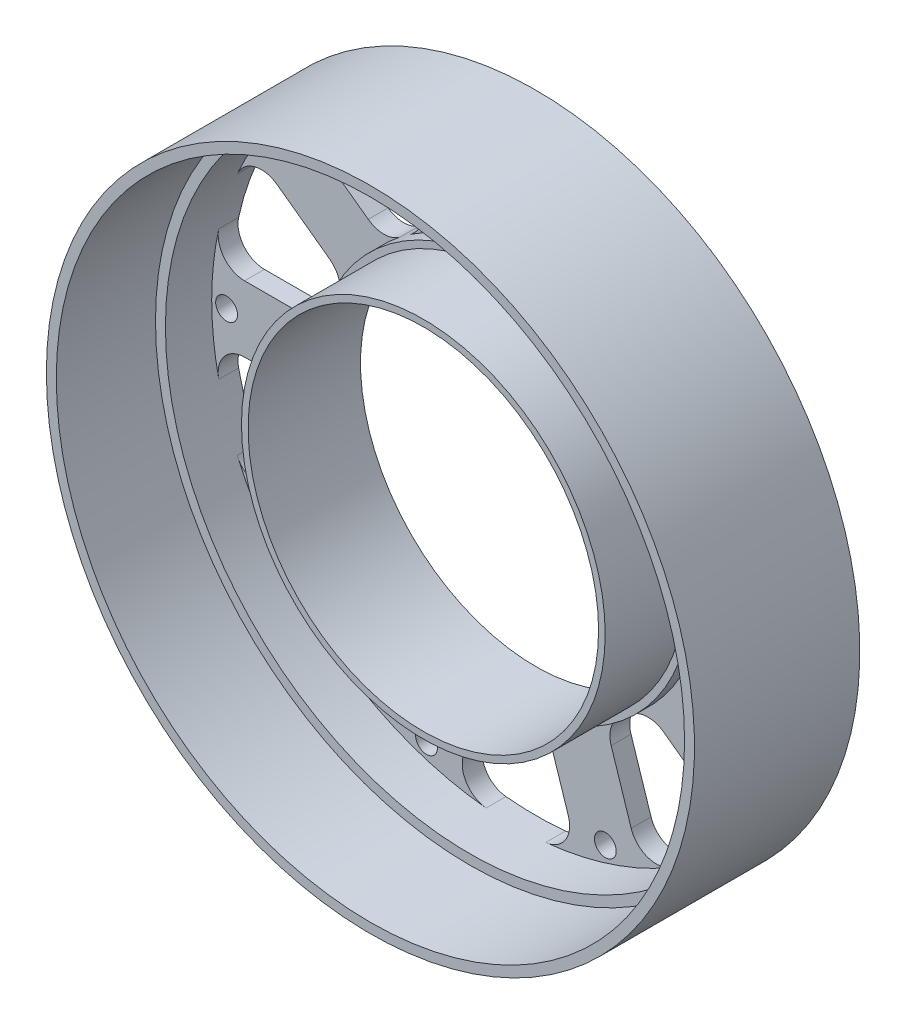
SolidWorks part; units mm, degrees
ref_plane "Front Plane" through (0, 0, 0) normal (0, 0, 1) x (1, 0, 0)
ref_plane "Top Plane" through (0, 0, 0) normal (0, 1, 0) x (1, 0, 0)
ref_plane "Right Plane" through (0, 0, 0) normal (1, 0, 0) x (0, 0, -1)
sketch "Sketch1" plane through (0, 0, 0) normal (0, 0, 1) x (1, 0, 0)
  circle A0 centre (0, 0) radius 27.5
  circle A1 centre (0, 0) radius 26.5
  circle A2 centre (0, 0) radius 28.5
  dimension "D1" = 55
  dimension "D2" = 53
  dimension "D3" = 57
extrude "Boss-Extrude2" add sketch "Sketch1" along normal blind 12 contours A0 A1 region at (-26.7222, 0, 0)
extrude "Boss-Extrude3" add sketch "Sketch1<3>" against normal blind 5 contours A2 A0 | A0 A1 region at (-26.7222, 0, 0) region at (-27.6939, 0, 0)
sketch "Sketch1<3>" plane through (0, 0, 0) normal (0, 0, 1) x (1, 0, 0) same geometry as "Sketch1"
sketch "Sketch3" plane through (0, 0, -5) normal (0, 0, -1) x (-1, 0, 0)
  line L0 (0, -1000) -> (0, 49000) construction
  line L1 (0, 0) -> (47.5, 0) construction
  line L2 (28.058, 5) -> (47.2361, 5)
  line L3 (28.058, -5) -> (47.2361, -5)
  line L4 (25.6383, -12.447) -> (41.1537, -23.7196)
  line L5 (19.7605, -20.5371) -> (35.2759, -31.8098)
  line L6 (13.4257, -25.1396) -> (19.352, -43.3791)
  line L7 (3.9151, -28.2298) -> (9.8415, -46.4693)
  line L8 (-3.9151, -28.2298) -> (-9.8415, -46.4693)
  line L9 (-13.4257, -25.1396) -> (-19.352, -43.3791)
  line L10 (-19.7605, -20.5371) -> (-35.2759, -31.8098)
  line L11 (-25.6383, -12.447) -> (-41.1537, -23.7196)
  line L12 (-28.058, -5) -> (-47.2361, -5)
  line L13 (-28.058, 5) -> (-47.2361, 5)
  line L14 (-25.6383, 12.447) -> (-41.1537, 23.7196)
  line L15 (-19.7605, 20.5371) -> (-35.2759, 31.8098)
  line L16 (-13.4257, 25.1396) -> (-19.352, 43.3791)
  line L17 (-3.9151, 28.2298) -> (-9.8415, 46.4693)
  line L18 (3.9151, 28.2298) -> (9.8415, 46.4693)
  line L19 (13.4257, 25.1396) -> (19.352, 43.3791)
  line L20 (19.7605, 20.5371) -> (35.2759, 31.8098)
  line L21 (25.6383, 12.447) -> (41.1537, 23.7196)
  circle A0 centre (0, 0) radius 28.5 construction
  arc A1 (28.058, -5) -> (28.058, 5) centre (0, 0) ccw
  circle A2 centre (0, 0) radius 47.5
  arc A3 (19.7605, -20.5371) -> (25.6383, -12.447) centre (0, 0) ccw
  arc A4 (3.9151, -28.2298) -> (13.4257, -25.1396) centre (0, 0) ccw
  arc A5 (-13.4257, -25.1396) -> (-3.9151, -28.2298) centre (0, 0) ccw
  arc A6 (-25.6383, -12.447) -> (-19.7605, -20.5371) centre (0, 0) ccw
  arc A7 (-28.058, 5) -> (-28.058, -5) centre (0, 0) ccw
  arc A8 (-19.7605, 20.5371) -> (-25.6383, 12.447) centre (0, 0) ccw
  arc A9 (-3.9151, 28.2298) -> (-13.4257, 25.1396) centre (0, 0) ccw
  arc A10 (13.4257, 25.1396) -> (3.9151, 28.2298) centre (0, 0) ccw
  arc A11 (25.6383, 12.447) -> (19.7605, 20.5371) centre (0, 0) ccw
  circle A12 centre (0, 0) radius 49
  circle A13 centre (0, 0) radius 46
  point P48 (0, 0)
  circle M7 centre (0, 0) radius 28.5
  dimension "D1" = 95
  dimension "D4" = 98
  dimension "D5" = 92
  dimension "D2" = 5
  dimension "D3" = 10
extrude "Boss-Extrude4" add sketch "Sketch3" against normal blind 3 contours L15 A2 L14 M7 | L17 A2 L16 M7 | L19 A2 L18 M7 | L21 A2 L20 M7 | L3 A2 L2 M7 | L5 A2 L4 M7 | L7 A2 L6 M7 | L9 A2 L8 M7 | L11 A2 L10 M7 | L13 A2 L12 M7 | A13 L17 A2 L16 | A13 L15 A2 L14 | A13 L19 A2 L18 | A13 L21 A2 L20 | A13 L3 A2 L2 | A13 L5 A2 L4 | A13 L7 A2 L6 | A13 L9 A2 L8 | A13 L11 A2 L10 | A13 L13 A2 L12 region at (-37.1309, 0, -5) region at (-46.6606, 0, -5) region at (-30.0395, 21.825, -5) region at (-37.7492, 27.4264, -5) region at (-30.0395, -21.825, -5) region at (-11.4741, 35.3136, -5) region at (-37.7492, -27.4264, -5) region at (-14.4189, 44.3768, -5) region at (-11.4741, -35.3136, -5) region at (11.4741, 35.3136, -5) region at (-14.4189, -44.3768, -5) region at (14.4189, 44.3768, -5) region at (11.4741, -35.3136, -5) region at (30.0395, 21.825, -5) region at (14.4189, -44.3768, -5) region at (37.7492, 27.4264, -5) region at (30.0395, -21.825, -5) region at (37.1309, 0, -5) region at (37.7492, -27.4264, -5) region at (46.6606, 0, -5)
extrude "Boss-Extrude5" add sketch "Sketch3<3>" against normal blind 25 contours A12 A2 region at (47.6141, 0, -5)
sketch "Sketch3<3>" plane through (0, 0, -5) normal (0, 0, -1) x (-1, 0, 0) same geometry as "Sketch3"
extrude "Boss-Extrude6" add sketch "Sketch3<5>" against normal blind 10 contours A13 L8 A2 L7 | A13 L10 A2 L9 | A13 L6 A2 L5 | A13 L4 A2 L3 | A13 L2 A2 L21 | A13 L20 A2 L19 | A13 L18 A2 L17 | A13 L16 A2 L15 | A13 L14 A2 L13 | A13 L12 A2 L11 | A13 L17 A2 L16 | A13 L15 A2 L14 | A13 L13 A2 L12 | A13 L19 A2 L18 | A13 L21 A2 L20 | A13 L3 A2 L2 | A13 L5 A2 L4 | A13 L7 A2 L6 | A13 L9 A2 L8 | A13 L11 A2 L10 region at (-44.1507, 14.3454, -5) region at (-46.6606, 0, -5) region at (-37.7492, 27.4264, -5) region at (-44.1507, -14.3454, -5) region at (-27.2867, 37.5569, -5) region at (-37.7492, -27.4264, -5) region at (-14.4189, 44.3768, -5) region at (-27.2867, -37.5569, -5) region at (0, 46.4228, -5) region at (-14.4189, -44.3768, -5) region at (14.4189, 44.3768, -5) region at (0, -46.4228, -5) region at (27.2867, 37.5569, -5) region at (14.4189, -44.3768, -5) region at (37.7492, 27.4264, -5) region at (27.2867, -37.5569, -5) region at (44.1507, 14.3454, -5) region at (37.7492, -27.4264, -5) region at (46.6606, 0, -5) region at (44.1507, -14.3454, -5)
sketch "Sketch3<5>" plane through (0, 0, -5) normal (0, 0, -1) x (-1, 0, 0) same geometry as "Sketch3"
fillet "Fillet1" radius 4 40 edges at (-34.0554, 30.923, -3.5) (-18.8858, 41.9443, -3.5) (-13.4257, 25.1396, -3.5) (-19.7605, 20.5371, -3.5) (-39.9332, 22.8328, -3.5) (-45.7275, 5, -3.5) (-25.6383, 12.447, -3.5) (-28.058, 5, -3.5) (-39.9332, -22.8328, -3.5) (-45.7275, -5, -3.5) (-28.058, -5, -3.5) (-25.6383, -12.447, -3.5) (-19.7605, -20.5371, -3.5) (-13.4257, -25.1396, -3.5) (-18.8858, -41.9443, -3.5) (-34.0554, -30.923, -3.5) (-9.3753, -45.0345, -3.5) (-3.9151, -28.2298, -3.5) (3.9151, -28.2298, -3.5) (9.3753, -45.0345, -3.5) (18.8858, -41.9443, -3.5) (34.0554, -30.923, -3.5) (19.7605, -20.5371, -3.5) (13.4257, -25.1396, -3.5) (28.058, -5, -3.5) (25.6383, -12.447, -3.5) (45.7275, -5, -3.5) (39.9332, -22.8328, -3.5) (28.058, 5, -3.5) (25.6383, 12.447, -3.5) (39.9332, 22.8328, -3.5) (45.7275, 5, -3.5) (19.7605, 20.5371, -3.5) (13.4257, 25.1396, -3.5) (18.8858, 41.9443, -3.5) (34.0554, 30.923, -3.5) (-3.9151, 28.2298, -3.5) (3.9151, 28.2298, -3.5) (-9.3753, 45.0345, -3.5) (9.3753, 45.0345, -3.5)
sketch "Sketch4" plane through (0, 0, -5) normal (0, 0, -1) x (-1, 0, 0)
  line L0 (0, 0) -> (43.75, 0) construction
  circle A0 centre (0, 0) radius 43.75 construction
  dimension "D1" = 87.5
hole_wizard "M4x0.7 Tapped Hole1" positions "Sketch5" profile "Sketch6" tap size "M4x0.7" standard "ANSI Metric" end condition through all
sketch "Sketch5" plane through (0, 0, -5) normal (0, 0, -1) x (-1, 0, 0)
  point P0 (43.75, 0)
sketch "Sketch6" plane through (-43.75, 0, -5) normal (1, 0, 0) x (0, 1, 0)
  line L0 (0, 0) -> (0, 25)
  line L1 (0, 25) -> (1.65, 25)
  line L2 (1.65, 25) -> (1.65, 0)
  line L5 (1.65, 0) -> (0, 0)
  line L11 (0, -6.35) -> (0, 107.95) construction
  dimension "Thru Tap Drill Dia." = 3.3
  dimension "Thru Tap Drill Depth" = 25
cosmetic thread "Hole Thread1" parameters "D2"=4
sketch "Sketch7" plane through (0, 0, 0) normal (1, 0, 0) x (0, 0, -1)
  line L0 (-1000, 0) -> (49000, 0) construction
pattern_circular "CirPattern1" count 10 over 360 about axis through (0, 0, 1000) along (0, 0, -1) of "M4x0.7 Tapped Hole1" reverse direction yes
cosmetic thread "Hole Thread2" parameters "D2"=4
cosmetic thread "Hole Thread3" parameters "D2"=4
cosmetic thread "Hole Thread4" parameters "D2"=4
cosmetic thread "Hole Thread5" parameters "D2"=4
cosmetic thread "Hole Thread6" parameters "D2"=4
cosmetic thread "Hole Thread7" parameters "D2"=4
cosmetic thread "Hole Thread8" parameters "D2"=4
cosmetic thread "Hole Thread9" parameters "D2"=4
cosmetic thread "Hole Thread10" parameters "D2"=4
